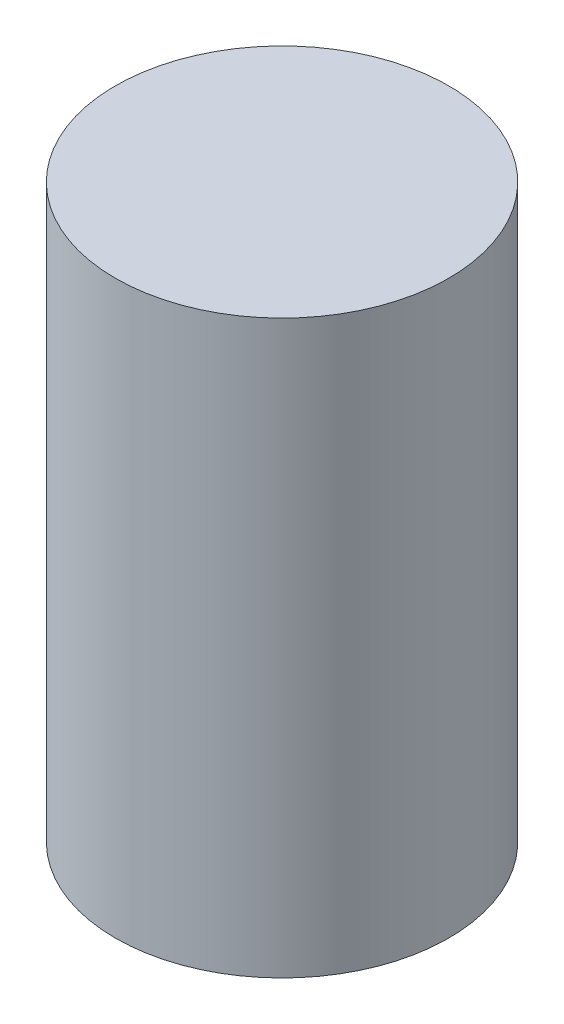
SolidWorks part; units mm, degrees
ref_plane "Front Plane" through (0, 0, 0) normal (0, 0, 1) x (1, 0, 0)
ref_plane "Top Plane" through (0, 0, 0) normal (0, 1, 0) x (1, 0, 0)
ref_plane "Right Plane" through (0, 0, 0) normal (1, 0, 0) x (0, 0, -1)
ref_axis "Axis1" through (0, 0, 0) along (0, 1, 0)
sketch "Sketch1" plane through (0, 0, 0) normal (0, 0, 1) x (1, 0, 0)
  line L0 (0, 0) -> (0, -35082.5666) construction
  line L3 (-2.5, 0) -> (-6.3, 0)
  line L4 (0, 0) -> (0, 21.6)
  line L5 (0, 21.6) -> (-6.3, 21.6)
  line L6 (-6.3, 0) -> (-6.3, 21.6)
  line L8 (0, 0) -> (0, -1.5)
  line L9 (0, -1.5) -> (-2.5, -1.5)
  line L10 (-2.5, 0) -> (-2.5, -1.5)
  dimension "D1" = 5
  dimension "D2" = 1.5
  dimension "D3" = 12.6
  dimension "D4" = 21.6
revolve "Revolve1" add sketch "Sketch1" angle 360 about L0
